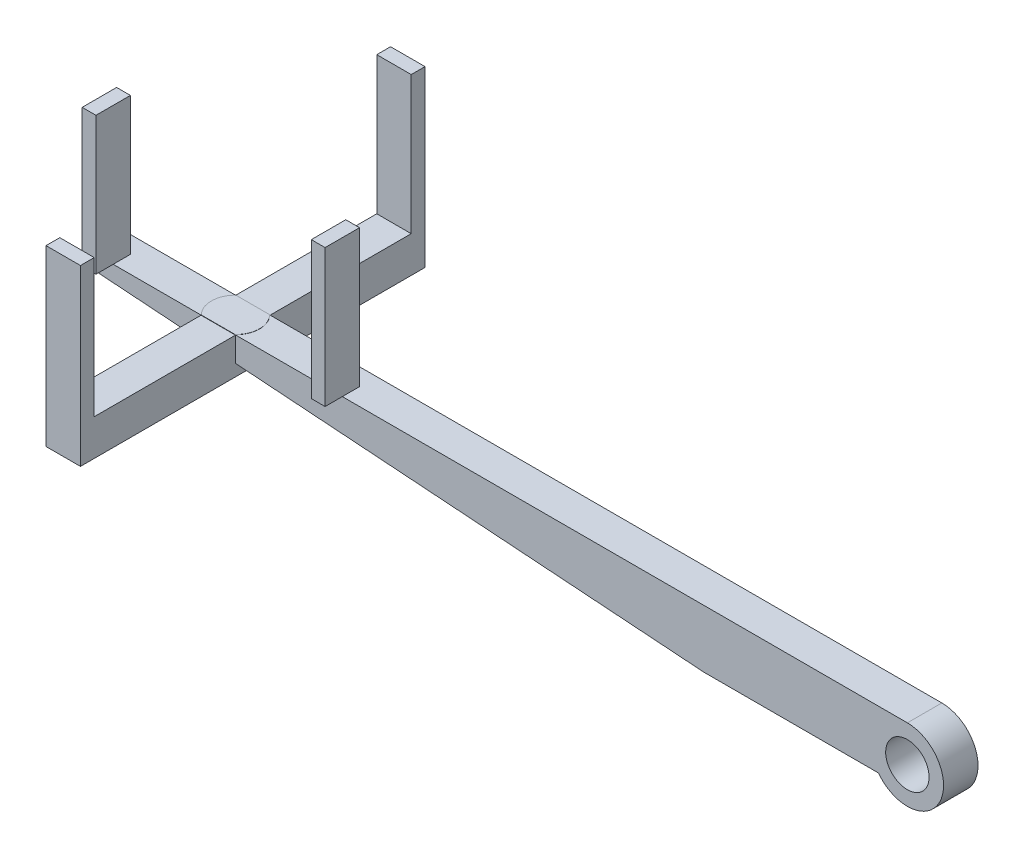
SolidWorks part; units mm, degrees
material "ABS"
ref_plane "Front Plane" through (0, 0, 0) normal (0, 0, 1) x (1, 0, 0)
ref_plane "Top Plane" through (0, 0, 0) normal (0, 1, 0) x (1, 0, 0)
ref_plane "Right Plane" through (0, 0, 0) normal (1, 0, 0) x (0, 0, -1)
sketch "Sketch1" plane through (0, 0, 0) normal (0, 0, 1) x (1, 0, 0)
  line L0 (0, 0) -> (-6.3, 0)
  line L1 (-6.3, 0) -> (-6.3, -236.5)
  line L2 (-6.3, -236.5) -> (6.3, -236.5)
  line L3 (6.3, -236.5) -> (6.3, 0)
  line L4 (6.3, 0) -> (0, 0)
  line L5 (6.3, 0) -> (10.5, 0)
  line L6 (10.5, 0) -> (10.5, -236.5)
  line L7 (10.5, -236.5) -> (6.3, -236.5)
  line L8 (-6.3, 0) -> (-10.5, 0)
  line L9 (-10.5, 0) -> (-10.5, -236.5)
  line L10 (-10.5, -236.5) -> (-6.3, -236.5)
  line L11 (10.5, 0) -> (-6.3, -236.5)
  circle A0 centre (0, 0) radius 6.3
  circle A1 centre (0, 0) radius 10.5
  dimension "D1" = 236.5
  dimension "D3" = 4.2
  dimension "D2" = 12.6
extrude "Boss-Extrude2" add sketch "Sketch1" along normal blind 10 contours A1 L1 L2 L3 | L1 A1 L3 A0 | A1 L9 L10 L1 | L8 A1 L1 | L3 A1 L5 | L5 A1 L8 A0 region at (0, -7.2256, 0) region at (-8.0126, -3.2551, 0) region at (-8.4, 0.2348, 0) region at (8.01, -3.2578, 0) region at (-1.3498, -88.3208, 0) region at (-8.4099, -121.1772, 0)
move or copy body "Body-Move/Copy1" bodies to move or copy 105 copy no rotation origin (-34.8, -34.75, 0) rotation axis (0, 0, -1) rotation angle 90
move or copy body "Body-Move/Copy2" bodies to move or copy 106 copy no translate (0, 69.6, 0)
sketch "Sketch3" plane through (0, 0, 0) normal (0, 1, 0) x (1, 0, 0)
  line L0 (0, 0) -> (-0.05, -5)
  line L1 (-0.05, -10) -> (-0.05, 0) construction
  line L2 (-0.05, -5) -> (-195.05, -5)
  line L4 (-195.05, -5) -> (-195.05, -55)
  line L7 (-195.05, -55) -> (-205.05, -55)
  line L8 (-205.05, -55) -> (-205.05, -45)
  line L10 (-195.05, -5) -> (-195.05, 45)
  line L11 (-195.05, 45) -> (-205.05, 45)
  line L12 (-205.05, 45) -> (-205.05, -45)
  dimension "D1" = 10
  dimension "D2" = 50
  dimension "D3" = 50
  dimension "D4" = 195
extrude "Boss-Extrude4" add sketch "Sketch3" along normal blind 10.5 contours L11 L12 L8 L7 L4 L10 region at (-200.05, 0, 5)
sketch "Sketch4" plane through (0, 10.55, 0) normal (0, 1, 0) x (1, 0, 0)
  line L0 (0, 0) -> (-0.05, -5)
  line L1 (-0.05, -10) -> (-0.05, 0) construction
  line L2 (-0.05, -5) -> (-200.05, -5)
  circle A0 centre (-200.05, -5) radius 7
  line M2 (-0.05, 0) -> (-236.55, 0)
  line M4 (-236.55, -10) -> (-0.05, -10)
  dimension "D1" = 200
extrude "Boss-Extrude5" add sketch "Sketch4" along normal blind 0.05 contours A0 M4 M2 region at (-193.7552, 10.55, 7.6451)
sketch "Sketch5" plane through (0, 0, 10) normal (0, 0, 1) x (1, 0, 0)
  line L0 (-0.05, 0.05) -> (-0.05, 10.55)
  line L1 (-0.05, 10.55) -> (-195.151, 10.55) construction
  line L2 (-0.05, 10.55) -> (-200.05, 10.5)
  line L3 (-195.05, 10.5) -> (-205.05, 10.5) construction
  line L4 (-200.05, 10.5) -> (-164.05, 10.509)
  line L5 (-164.05, 10.509) -> (-164.05, 50.508)
  line L6 (-164.05, 50.508) -> (-168.05, 50.508)
  line L7 (-168.05, 50.508) -> (-168.05, 10.508)
  line L8 (-200.05, 10.5) -> (-234.5529, 10.55)
  line L9 (-204.949, 10.55) -> (-236.55, 10.55) construction
  line L10 (-234.5529, 10.55) -> (-234.5529, 50.508)
  line L11 (-234.5529, 50.508) -> (-230.5529, 50.508)
  line L12 (-230.5529, 50.508) -> (-230.5529, 10.5442)
  arc A0 (-0.05, -10.45) -> (-0.05, 10.55) centre (-0.05, 0.05) ccw construction
  line M16 (-0.05, 10.55) -> (-195.151, 10.55)
  line M20 (-204.949, 10.55) -> (-236.55, 10.55)
  dimension "D1" = 4
  dimension "D2" = 36
  dimension "D3" = 40
  dimension "D4" = 4
  dimension "D5" = 39.9638
  dimension "D6" = 39.958
move or copy body "Body-Move/Copy4" bodies to move or copy 123 copy no translate (0, 0, -5)
extrude "Boss-Extrude6" add sketch "Sketch5" against normal blind 10 contours L6 L7 L5 M16 | L12 L11 L10 M20 region at (-166.05, 30.529, 10) region at (-232.5529, 30.529, 10)
sketch "Sketch6" plane through (-205.05, 0, 0) normal (-1, 0, 0) x (0, 0, 1)
  line L0 (-50, 10.5) -> (-50, 50.5)
  line L1 (-50, 10.5) -> (-5, 10.5) construction
  line L2 (-46, 10.5) -> (-50, 10.5)
  line L6 (-50, 50.5) -> (-46, 50.5)
  line L7 (-46, 50.5) -> (-46, 10.5)
  line L8 (50, 10.5) -> (46, 10.5)
  line L9 (5, 10.5) -> (50, 10.5) construction
  line L10 (46, 10.5) -> (46, 50.5)
  line L11 (46, 50.5) -> (50, 50.5)
  line L12 (50, 50.5) -> (50, 10.5)
  dimension "D1" = 4
  dimension "D2" = 4
  dimension "D3" = 40
extrude "Boss-Extrude7" add sketch "Sketch6" against normal blind 10
